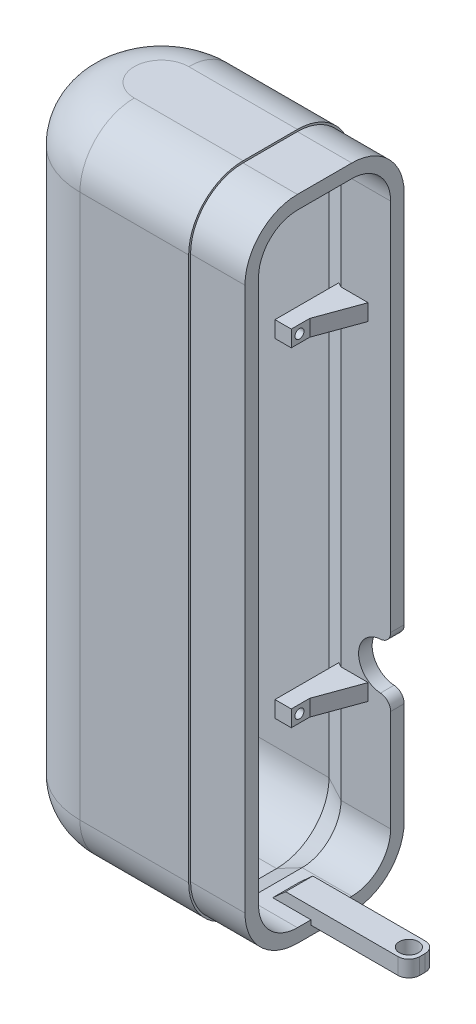
SolidWorks part; units mm, degrees
ref_plane "Front Plane" through (0, 0, 0) normal (0, 0, 1) x (1, 0, 0)
ref_plane "Top Plane" through (0, 0, 0) normal (0, 1, 0) x (1, 0, 0)
ref_plane "Right Plane" through (0, 0, 0) normal (1, 0, 0) x (0, 0, -1)
sketch "Sketch1" plane through (0, 0, 0) normal (0, 1, 0) x (1, 0, 0)
  line L0 (0, 19.05) -> (0, -19.05) construction
  line L1 (0, -19.05) -> (25.4, -19.05)
  line L2 (25.4, -19.05) -> (25.4, 19.05)
  line L3 (25.4, 19.05) -> (0, 19.05)
  arc A0 (0, 19.05) -> (0, -19.05) centre (0, 0) ccw
  dimension "D1" = 38.1
  dimension "D2" = 25.4
extrude "Boss-Extrude1" add sketch "Sketch1" along normal mid plane 152.4
fillet "Fillet1" radius 12.7 6 edges at (12.7, 76.2, -19.05) (12.7, 76.2, 19.05) (12.7, -76.2, -19.05) (12.7, -76.2, 19.05) (-19.05, 76.2, 0) (-19.05, -76.2, 0)
shell "Shell1" thickness 0.4508 removed face at (25.4, 0, 0)
sketch "Sketch4" plane through (25.4, 0, 0) normal (1, 0, 0) x (0, 0, -1)
  line L0 (6.35, -75.7492) -> (-6.35, -75.7492) construction
  line L1 (-18.5992, 63.5) -> (-18.5992, -63.5) construction
  line L2 (18.5992, -63.5) -> (18.5992, 63.5) construction
  line L3 (-6.35, 75.7492) -> (6.35, 75.7492) construction
  line L4 (6.35, -75.7492) -> (-6.35, -75.7492)
  line L5 (-18.5992, 63.5) -> (-18.5992, -63.5)
  line L6 (18.5992, -63.5) -> (18.5992, 63.5)
  line L7 (-6.35, 75.7492) -> (6.35, 75.7492)
  arc A1 (-18.5992, -63.5) -> (-6.35, -75.7492) centre (-6.35, -63.5) ccw construction
  arc A2 (6.35, -75.7492) -> (18.5992, -63.5) centre (6.35, -63.5) ccw construction
  arc A3 (-6.35, 75.7492) -> (-18.5992, 63.5) centre (-6.35, 63.5) ccw construction
  arc A4 (18.5992, 63.5) -> (6.35, 75.7492) centre (6.35, 63.5) ccw construction
  arc A5 (-18.5992, -63.5) -> (-6.35, -75.7492) centre (-6.35, -63.5) ccw
  arc A6 (6.35, -75.7492) -> (18.5992, -63.5) centre (6.35, -63.5) ccw
  arc A7 (-6.35, 75.7492) -> (-18.5992, 63.5) centre (-6.35, 63.5) ccw
  arc A8 (18.5992, 63.5) -> (6.35, 75.7492) centre (6.35, 63.5) ccw
extrude "Extrude-Thin1" add sketch "Sketch4" along normal blind 12.7 and the other way blind 6.35 thin thin type one direction reverse wall 3.175
chamfer "Chamfer1" distance 7.46 angle 28 8 edges at (19.05, 0, -15.4242) (19.05, 69.9164, -12.7664) (19.05, -69.9164, -12.7664) (19.05, 72.5742, 0) (19.05, -72.5742, 0) (19.05, 69.9164, 12.7664) (19.05, -69.9164, 12.7664) (19.05, 0, 15.4242) first distance on face at (28.575, 0, -15.4242) first distance on face at (28.575, 68.9768, -11.8268) first distance on face at (28.575, -68.9768, -11.8268) first distance on face at (28.575, 72.5742, 0) first distance on face at (28.575, -72.5742, 0) first distance on face at (28.575, 68.9768, 11.8268) first distance on face at (28.575, -68.9768, 11.8268) first distance on face at (28.575, 0, 15.4242)
sketch "Sketch6" plane through (25.4, 0, 0) normal (1, 0, 0) x (0, 0, -1)
  line L1 (1.1107, 40.3365) -> (18.5992, 40.3365)
  line L2 (1.1107, 40.3365) -> (1.1107, 36.5265)
  line L3 (1.1107, 36.5265) -> (18.5992, 36.5265)
  line L4 (18.5992, 40.3365) -> (18.5992, 36.5265)
  line L5 (1.1107, -36.506) -> (4.9207, -40.316) construction
  line L6 (1.1107, -36.506) -> (18.5992, -36.506)
  line L7 (1.1107, -36.506) -> (1.1107, -40.316)
  line L8 (1.1107, -40.316) -> (18.5992, -40.316)
  line L9 (18.5992, -36.506) -> (18.5992, -40.316)
  line L10 (1.1107, 40.3365) -> (4.9207, 36.5265) construction
  line L11 (18.5992, -63.5) -> (18.5992, 63.5) construction
  line L12 (18.5992, 63.5) -> (18.5992, -63.5) construction
  circle A0 centre (3.0157, 38.4315) radius 1.0543 construction
  circle A1 centre (3.0157, -38.411) radius 1.0543 construction
  circle A2 centre (3.0157, 38.4315) radius 1.0543
  circle A3 centre (3.0157, -38.411) radius 1.0543
  point P16 (3.0157, 38.4315)
  point P19 (3.0157, -38.411)
  dimension "D1" = 45
  dimension "D2" = 3.81
extrude "Boss-Extrude3" add sketch "Sketch6" along normal blind 3.81
chamfer "Chamfer2" distance 10 angle 20 2 edges at (29.21, 38.4315, -15.4242) (29.21, -38.411, -15.4242) first distance on face at (29.21, 38.4315, -4.07) first distance on face at (29.21, -38.411, -4.07)
ref_plane "Plane2" through (0, -73.66, 0) normal (0, -1, 0) x (-1, 0, 0)
sketch "Sketch7" plane through (0, -73.66, 0) normal (0, 1, 0) x (1, 0, 0)
  line L0 (38.1, 6.35) -> (38.1, -6.35) construction
  line L1 (27.94, -3.175) -> (60.96, -3.175)
  line L2 (27.94, -3.175) -> (27.94, 3.175)
  line L3 (27.94, 3.175) -> (60.96, 3.175)
  line L4 (60.96, -3.175) -> (60.96, 3.175)
  line L5 (27.94, -3.175) -> (60.96, 3.175) construction
  line L6 (27.94, 3.175) -> (60.96, -3.175) construction
  point P0 (44.45, 0)
  dimension "D1" = 10.16
  dimension "D2" = 6.35
  dimension "D3" = 22.86
extrude "Boss-Extrude4" add sketch "Sketch7" along normal blind 3.81
chamfer "Chamfer3" distance 3.81 angle 48 1 edges at (27.94, -69.85, 0) first distance on face at (27.94, -71.2121, 0)
sketch "Sketch8" plane through (0, -69.85, 0) normal (0, 1, 0) x (1, 0, 0)
  line L0 (60.96, 3.175) -> (54.61, -3.175) construction
  line L1 (32.1714, -3.175) -> (60.96, -3.175) construction
  circle A0 centre (57.785, 0) radius 2.25
  dimension "D2" = 4.5
  dimension "D1" = 45
extrude "Cut-Extrude1" cut sketch "Sketch8" against normal through all
fillet "Fillet2" radius 2.54 2 edges at (60.96, -71.755, -3.175) (60.96, -71.755, 3.175)
sketch "Sketch9" plane through (0, 0, -15.4242) normal (0, 0, 1) x (1, 0, 0)
  circle A0 centre (36.068, -31.75) radius 2.921 construction
  circle A1 centre (36.068, -31.75) radius 2.921 construction
  circle A2 centre (36.068, -31.75) radius 5.461
  dimension "D1" = 2.54
extrude "Cut-Extrude2" cut sketch "Sketch9" against normal through all
fillet "Fillet3" radius 2.54 2 edges at (38.1, -36.8189, -17.0117) (38.1, -26.6811, -17.0117)
